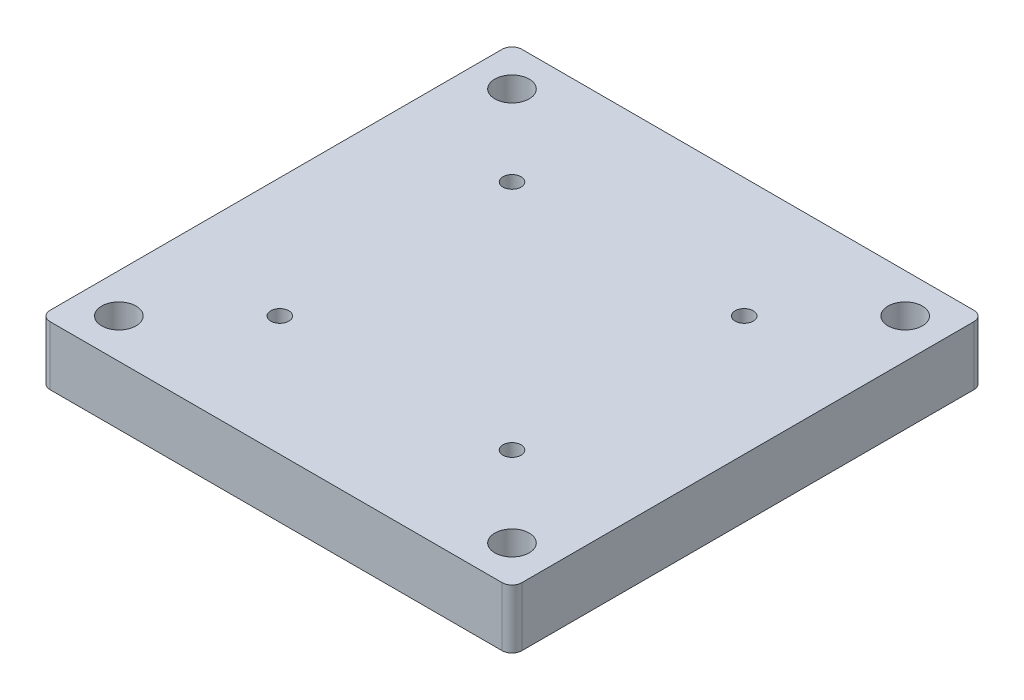
SolidWorks part; units mm, degrees
material "Delrin 2700 NC010, Low Viscosity Acetal Copolymer (SS)"
ref_plane "Front" through (0, 0, 0) normal (0, 0, 1) x (1, 0, 0)
ref_plane "Top" through (0, 0, 0) normal (0, 1, 0) x (1, 0, 0)
ref_plane "Right" through (0, 0, 0) normal (1, 0, 0) x (0, 0, -1)
sketch "Sketch1" plane through (0, 0, 0) normal (0, 1, 0) x (1, 0, 0)
  line L1 (-76.2, 76.2) -> (76.2, 76.2)
  line L2 (-76.2, 76.2) -> (-76.2, -76.2)
  line L3 (-76.2, -76.2) -> (76.2, -76.2)
  line L4 (76.2, 76.2) -> (76.2, -76.2)
  line L5 (-76.2, 76.2) -> (76.2, -76.2) construction
  line L6 (-76.2, -76.2) -> (76.2, 76.2) construction
  point P0 (0, 0)
  dimension "D1" = 152.4
  dimension "D2" = 152.4
extrude "Boss-Extrude1" add sketch "Sketch1" along normal blind 19.05
hole_wizard "CBORE for 1/4 Socket Head Cap Screw1" positions "Sketch2" profile "Sketch3" counterbore size "1/4" standard "ANSI Inch" end condition through all
sketch "Sketch2" plane through (0, 19.05, 0) normal (0, 1, 0) x (1, 0, 0)
  line L1 (-63.5, 63.5) -> (63.5, 63.5) construction
  line L2 (-63.5, 63.5) -> (-63.5, -63.5) construction
  line L3 (-63.5, -63.5) -> (63.5, -63.5) construction
  line L4 (63.5, 63.5) -> (63.5, -63.5) construction
  line L5 (-63.5, 63.5) -> (63.5, -63.5) construction
  line L6 (-63.5, -63.5) -> (63.5, 63.5) construction
  point P0 (-63.5, 63.5)
  point P2 (63.5, 63.5)
  point P4 (63.5, -63.5)
  point P6 (-63.5, -63.5)
  point P108 (0, 0)
  dimension "D1" = 127
  dimension "D2" = 127
sketch "Sketch3" plane through (-63.5, 19.05, -63.5) normal (1, 0, 0) x (0, 0, 1)
  line L0 (0, 0) -> (0, 19.05)
  line L1 (0, 19.05) -> (3.2639, 19.05)
  line L3 (3.2639, 19.05) -> (3.2639, 8.89)
  line L4 (3.2639, 8.89) -> (5.5562, 8.89)
  line L5 (5.5562, 8.89) -> (5.5562, 0)
  line L7 (5.5562, 0) -> (0, 0)
  line L11 (0, -6.35) -> (0, 107.95) construction
  dimension "Thru Hole Dia." = 6.5278
  dimension "Thru Hole Depth" = 19.05
  dimension "C'Bore Dia." = 11.1125
  dimension "C'Bore Depth" = 8.89
sketch "Sketch4" plane through (0, 0, 76.2) normal (0, 0, 1) x (1, 0, 0)
  line L0 (-31.9484, 19.05) -> (-31.9484, 12.7)
  line L1 (-76.2, 19.05) -> (76.2, 19.05) construction
  line L2 (-31.9484, 12.7) -> (-35.7188, 12.7)
  line L3 (-35.7188, 12.7) -> (-35.7188, 6.7469)
  line L4 (-35.7188, 6.7469) -> (-21.4312, 6.7469)
  line L5 (-21.4312, 6.7469) -> (-21.4312, 12.7)
  line L6 (-21.4312, 12.7) -> (-25.2016, 12.7)
  line L7 (-25.2016, 12.7) -> (-25.2016, 19.05)
  line L8 (0, 0) -> (0, 19.05) construction
  line L9 (-28.575, 6.7469) -> (-28.575, 19.05) construction
  line L10 (28.575, 6.7469) -> (28.575, 19.05) construction
  line L11 (25.2016, 12.7) -> (25.2016, 19.05)
  line L12 (21.4312, 12.7) -> (25.2016, 12.7)
  line L13 (21.4312, 6.7469) -> (21.4312, 12.7)
  line L14 (35.7188, 6.7469) -> (21.4312, 6.7469)
  line L15 (35.7188, 12.7) -> (35.7188, 6.7469)
  line L16 (31.9484, 12.7) -> (35.7188, 12.7)
  line L17 (31.9484, 19.05) -> (31.9484, 12.7)
  line L18 (-31.9484, 19.05) -> (-25.2016, 19.05)
  line L19 (25.2016, 19.05) -> (31.9484, 19.05)
  line L20 (-76.2, 0) -> (76.2, 0) construction
  dimension "D1" = 14.2875
  dimension "D2" = 6.7469
  dimension "D3" = 6.35
  dimension "D4" = 57.15
  dimension "D5" = 5.9531
  dimension "D6" = 6.7469
extrude "T-SLOT CUT WITH MCMASTER 8789A16 BIT" [suppressed] cut sketch "Sketch4" against normal through all
fillet "Fillet1" radius 3.175 4 edges at (-76.2, 9.525, 76.2) (76.2, 9.525, 76.2) (76.2, 9.525, -76.2) (-76.2, 9.525, -76.2)
hole_wizard "CBORE for #10 Button Head Cap Screw1" positions "Sketch5" profile "Sketch6" counterbore size "#10" standard "ANSI Inch" end condition through all
sketch "Sketch5" plane through (0, 0, 0) normal (0, -1, 0) x (-1, 0, 0)
  line L1 (37.5, -37.5) -> (-37.5, -37.5) construction
  line L2 (37.5, -37.5) -> (37.5, 37.5) construction
  line L3 (37.5, 37.5) -> (-37.5, 37.5) construction
  line L4 (-37.5, -37.5) -> (-37.5, 37.5) construction
  line L5 (37.5, -37.5) -> (-37.5, 37.5) construction
  line L6 (37.5, 37.5) -> (-37.5, -37.5) construction
  point P0 (37.5, -37.5)
  point P2 (-37.5, -37.5)
  point P4 (37.5, 37.5)
  point P6 (-37.5, 37.5)
  dimension "D1" = 75
  dimension "D2" = 75
sketch "Sketch6" plane through (-37.5, 0, 37.5) normal (1, 0, 0) x (0, 0, -1)
  line L0 (0, 0) -> (0, 19.05)
  line L1 (0, 19.05) -> (2.921, 19.05)
  line L3 (2.921, 19.05) -> (2.921, 7.874)
  line L4 (2.921, 7.874) -> (5.2705, 7.874)
  line L5 (5.2705, 7.874) -> (5.2705, 0)
  line L7 (5.2705, 0) -> (0, 0)
  line L11 (0, -6.35) -> (0, 107.95) construction
  dimension "Thru Hole Dia." = 5.842
  dimension "Thru Hole Depth" = 19.05
  dimension "C'Bore Dia." = 10.541
  dimension "C'Bore Depth" = 7.874
